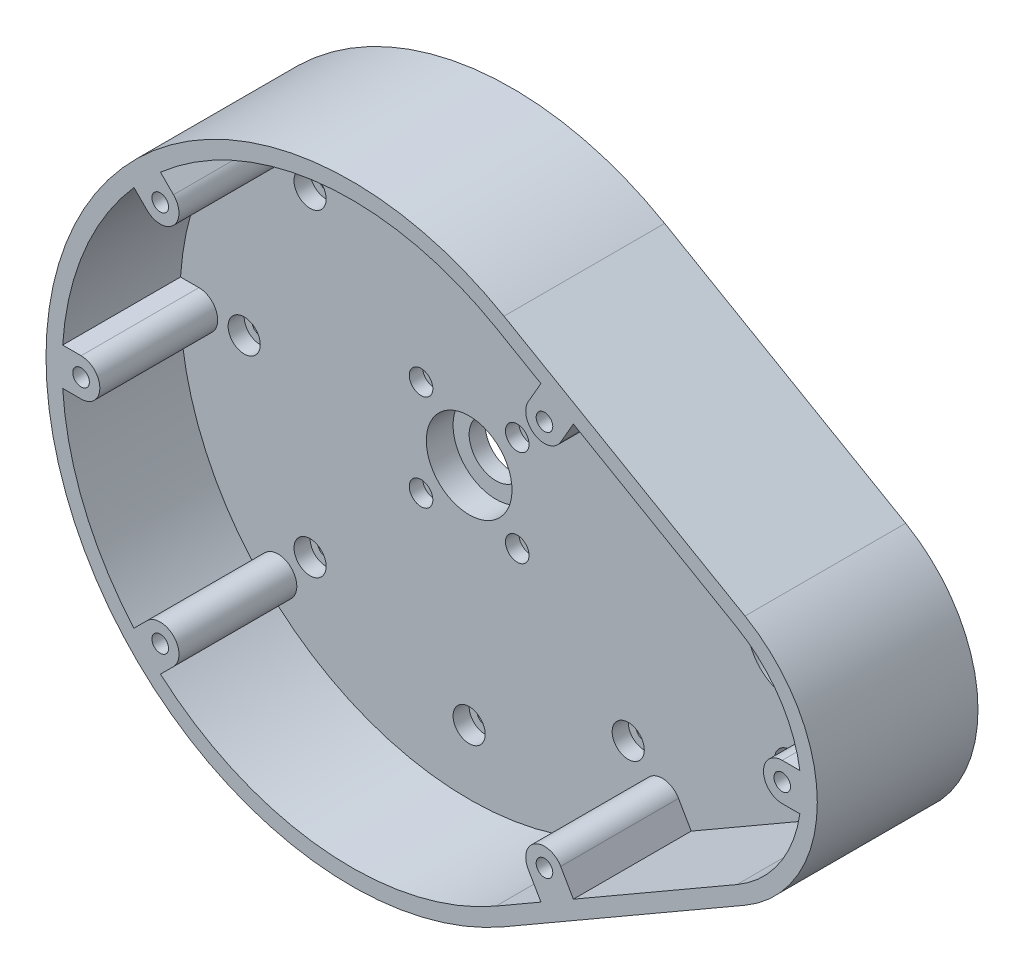
SolidWorks part; units mm, degrees
ref_plane "Front Plane" through (0, 0, 0) normal (0, 0, 1) x (1, 0, 0)
ref_plane "Top Plane" through (0, 0, 0) normal (0, 1, 0) x (1, 0, 0)
ref_plane "Right Plane" through (0, 0, 0) normal (1, 0, 0) x (0, 0, -1)
sketch "Sketch1" plane through (0, 0, 0) normal (0, 0, 1) x (1, 0, 0)
  line L0 (-30, 0) -> (30, 0) construction
  line L3 (-1.5, 49.3634) -> (43.5, 23.3827)
  line L4 (-1.5, -49.3634) -> (43.5, -23.3827)
  circle A0 centre (-30, 0) radius 57 construction
  circle A1 centre (30, 0) radius 27 construction
  circle A4 centre (-30, 0) radius 46.5 construction
  circle A5 centre (30, 0) radius 16.5 construction
  arc A6 (-1.5, 49.3634) -> (-1.5, -49.3634) centre (-30, 0) ccw
  arc A7 (43.5, 23.3827) -> (43.5, -23.3827) centre (30, 0) cw
  point P4 (0, 0)
extrude "Boss-Extrude1" add sketch "Sketch1" along normal blind 30 contours L4 A7 L3 A6
sketch "Sketch3" plane through (0, 0, 30) normal (0, 0, 1) x (1, 0, 0)
  line L3 (-3, -46.7654) -> (5.4002, -41.9155)
  line L4 (42, 20.7846) -> (11.4624, 38.4155)
  line L7 (-63.1987, -38.1484) -> (-65.6286, -40.5784)
  line L10 (-30, 0) -> (-65.6735, 35.6735) construction
  line L11 (-68.1484, 33.1987) -> (-63.1987, 38.1484) construction
  line L29 (-80.45, 3.5) -> (-83.8865, 3.5)
  line L30 (-80.45, -3.5) -> (-83.8865, -3.5)
  line L34 (-68.1484, 33.1987) -> (-70.5784, 35.6286)
  line L36 (-63.1987, 38.1484) -> (-65.6286, 40.5784)
  line L37 (-30, 0) -> (-65.6735, -35.6735) construction
  line L38 (30, 0) -> (50.45, 0.0259) construction
  line L45 (50.45, 3.5259) -> (53.7396, 3.5259)
  line L46 (50.45, -3.4741) -> (53.7472, -3.4741)
  line L49 (-63.1987, -38.1484) -> (-68.1484, -33.1987) construction
  line L50 (-68.1484, -33.1987) -> (-70.5784, -35.6286)
  line L54 (-80.45, 0) -> (-30, 0) construction
  line L57 (-30, 0) -> (6.0624, 36.0624) construction
  line L58 (3.0314, 37.8124) -> (9.0935, 34.3124) construction
  line L59 (9.0935, 34.3124) -> (11.4624, 38.4155)
  line L63 (3.0314, 37.8124) -> (5.4002, 41.9155)
  line L64 (5.4002, 41.9155) -> (-3, 46.7654)
  line L65 (-30, 0) -> (6.0624, -36.0624) construction
  line L66 (3.0314, -37.8124) -> (9.0935, -34.3124) construction
  line L67 (3.0314, -37.8124) -> (5.4002, -41.9155)
  line L68 (9.0935, -34.3124) -> (11.4624, -38.4155)
  line L69 (11.4624, -38.4155) -> (42, -20.7846)
  arc A12 (50.45, -3.4741) -> (50.45, 3.5259) centre (50.45, 0.0259) cw
  circle A13 centre (50.45, 0.0259) radius 1.55
  circle A41 centre (-80.45, 0) radius 1.55
  arc A42 (-80.45, 3.5) -> (-80.45, -3.5) centre (-80.45, 0) cw
  arc A61 (-3, 46.7654) -> (-65.6286, 40.5784) centre (-30, 0) ccw
  arc A62 (-83.8865, -3.5) -> (-70.5784, -35.6286) centre (-30, 0) ccw
  circle A64 centre (-65.6735, 35.6735) radius 1.55
  arc A65 (42, 20.7846) -> (53.7396, 3.5259) centre (30, 0) cw
  arc A66 (53.7472, -3.4741) -> (42, -20.7846) centre (30, 0) cw
  arc A67 (-68.1484, 33.1987) -> (-63.1987, 38.1484) centre (-65.6735, 35.6735) ccw
  arc A68 (-70.5784, 35.6286) -> (-83.8865, 3.5) centre (-30, 0) ccw
  circle A69 centre (-65.6735, -35.6735) radius 1.55
  arc A70 (-68.1484, -33.1987) -> (-63.1987, -38.1484) centre (-65.6735, -35.6735) cw
  arc A71 (-65.6286, -40.5784) -> (-3, -46.7654) centre (-30, 0) ccw
  circle A72 centre (6.0624, 36.0624) radius 1.55
  arc A73 (3.0314, 37.8124) -> (9.0935, 34.3124) centre (6.0624, 36.0624) ccw
  circle A74 centre (6.0624, -36.0624) radius 1.55
  arc A75 (3.0314, -37.8124) -> (9.0935, -34.3124) centre (6.0624, -36.0624) cw
  point P10 (-30, 0)
  point P20 (-30, 0)
  point P22 (-30, 0)
  point P30 (-65.6735, 35.6735)
  point P32 (-30, 0)
  point P35 (-30, 0)
  point P37 (-30, 0)
  point P39 (-30, 0)
  point P42 (-65.6735, -35.6735)
  point P48 (6.0624, 36.0624)
  point P51 (-30, 0)
  point P58 (6.0624, -36.0624)
  point P59 (-30, 0)
extrude "Cut-Extrude1" cut sketch "Sketch3" against normal blind 22
sketch "Sketch5" plane through (0, 0, 0) normal (0, 0, -1) x (-1, 0, 0)
  circle A13 centre (80.45, 0) radius 1.55
  circle A15 centre (-50.45, 0.0259) radius 1.55
  circle A20 centre (-6.0624, -36.0624) radius 1.55
  circle A21 centre (-6.0624, 36.0624) radius 1.55
  circle A22 centre (65.6735, 35.6735) radius 1.55
  circle A25 centre (65.6735, -35.6735) radius 1.55
extrude "Cut-Extrude2" cut sketch "Sketch5" against normal blind 30
sketch "Sketch6" plane through (0, 0, 0) normal (0, 0, -1) x (-1, 0, 0)
  circle A12 centre (-50.45, 0.0259) radius 3
  circle A15 centre (80.45, 0) radius 3
  circle A20 centre (65.6735, 35.6735) radius 3
  circle A21 centre (-6.0624, 36.0624) radius 3
  circle A22 centre (65.6735, -35.6735) radius 3
  circle A23 centre (-6.0624, -36.0624) radius 3
extrude "Cut-Extrude3" cut sketch "Sketch6" against normal blind 5
sketch "Sketch7" plane through (0, 0, 8) normal (0, 0, 1) x (1, 0, 0)
  line L0 (30, 0) -> (-30, 0) construction
  circle A4 centre (-30, 0) radius 8
  circle A9 centre (30, 0) radius 8
  point P5 (0, 0)
extrude "Cut-Extrude10" cut sketch "Sketch7" against normal blind 5
sketch "Sketch8" plane through (0, 0, 8) normal (0, 0, 1) x (1, 0, 0)
  line L0 (-30, 0) -> (-38.9803, 8.9803) construction
  circle A0 centre (-30, 0) radius 5
  circle A1 centre (-30, 0) radius 12.7 construction
  circle A2 centre (-38.9803, 8.9803) radius 1.05
  circle A3 centre (-21.0197, 8.9803) radius 1.05
  circle A4 centre (-21.0197, -8.9803) radius 1.05
  circle A5 centre (-38.9803, -8.9803) radius 1.05
  point P7 (-30, 0)
  point P10 (-30, 0)
  point P17 (-30, 0)
  dimension "D1" = 4
extrude "Cut-Extrude7" cut sketch "Sketch8" against normal blind 8
sketch "Sketch9" plane through (0, 0, 8) normal (0, 0, 1) x (1, 0, 0)
  circle A0 centre (-38.9803, 8.9803) radius 2.2
  circle A1 centre (-21.0197, 8.9803) radius 2.2
  circle A2 centre (-21.0197, -8.9803) radius 2.2
  circle A3 centre (-38.9803, -8.9803) radius 2.2
  point P12 (-30, 0)
  dimension "D1" = 4
extrude "Cut-Extrude8" cut sketch "Sketch9" against normal blind 2.5
sketch "Sketch10" plane through (0, 0, 30) normal (0, 0, 1) x (1, 0, 0)
  line L0 (-3.0003, 46.7655) -> (42, 20.7849)
  line L2 (-3.0003, -46.7655) -> (42, -20.7849)
  line L3 (-4, 45.0333) -> (41, 19.0526)
  line L4 (-4, -45.0333) -> (41, -19.0526)
  circle A0 centre (-30, 0) radius 54 construction
  circle A1 centre (30, 0) radius 24.0003 construction
  arc A2 (-3.0003, 46.7655) -> (-3.0003, -46.7655) centre (-30, 0) ccw
  arc A3 (42, 20.7849) -> (42, -20.7849) centre (30, 0) cw
  circle A4 centre (-30, 0) radius 52 construction
  circle A5 centre (30, 0) radius 22 construction
  arc A6 (41, 19.0526) -> (41, -19.0526) centre (30, 0) cw
  arc A7 (-4, 45.0333) -> (-4, -45.0333) centre (-30, 0) ccw
sketch "Sketch11" plane through (0, 0, 8) normal (0, 0, 1) x (1, 0, 0)
  line L0 (-30, 0) -> (-0.3015, 29.6985) construction
  line L1 (30, -19) -> (30, 19) construction
  line L2 (30, 0) -> (42, 0) construction
  line L3 (30, 0) -> (42, 0) construction
  circle A0 centre (-30, 0) radius 42 construction
  circle A1 centre (-0.3015, 29.6985) radius 1.55
  circle A2 centre (-30, 42) radius 1.55
  circle A3 centre (-59.6985, 29.6985) radius 1.55
  circle A4 centre (-72, 0) radius 1.55
  circle A5 centre (-59.6985, -29.6985) radius 1.55
  circle A6 centre (-30, -42) radius 1.55
  circle A7 centre (-0.3015, -29.6985) radius 1.55
  circle A8 centre (30, 19) radius 1.55
  circle A9 centre (30, -19) radius 1.55
  circle A10 centre (42, 0) radius 1.55
  point P19 (-30, 0)
  point P24 (30, 0)
  point P29 (30, 0)
  dimension "D1" = 7
extrude "Cut-Extrude11" cut sketch "Sketch11" against normal blind 8
sketch "Sketch12" plane through (0, 0, 8) normal (0, 0, 1) x (1, 0, 0)
  line L0 (-0.3015, 29.6985) -> (-30, 0) construction
  circle A0 centre (-0.3015, 29.6985) radius 3
  circle A1 centre (-30, 42) radius 3
  circle A2 centre (-59.6985, 29.6985) radius 3
  circle A3 centre (-72, 0) radius 3
  circle A4 centre (-59.6985, -29.6985) radius 3
  circle A5 centre (-30, -42) radius 3
  circle A6 centre (-0.3015, -29.6985) radius 3
  circle A7 centre (30, 19) radius 3
  circle A8 centre (42, 0) radius 3
  circle A9 centre (30, -19) radius 3
  point P20 (-30, 0)
  dimension "D1" = 7
extrude "Cut-Extrude12" cut sketch "Sketch12" against normal blind 3
